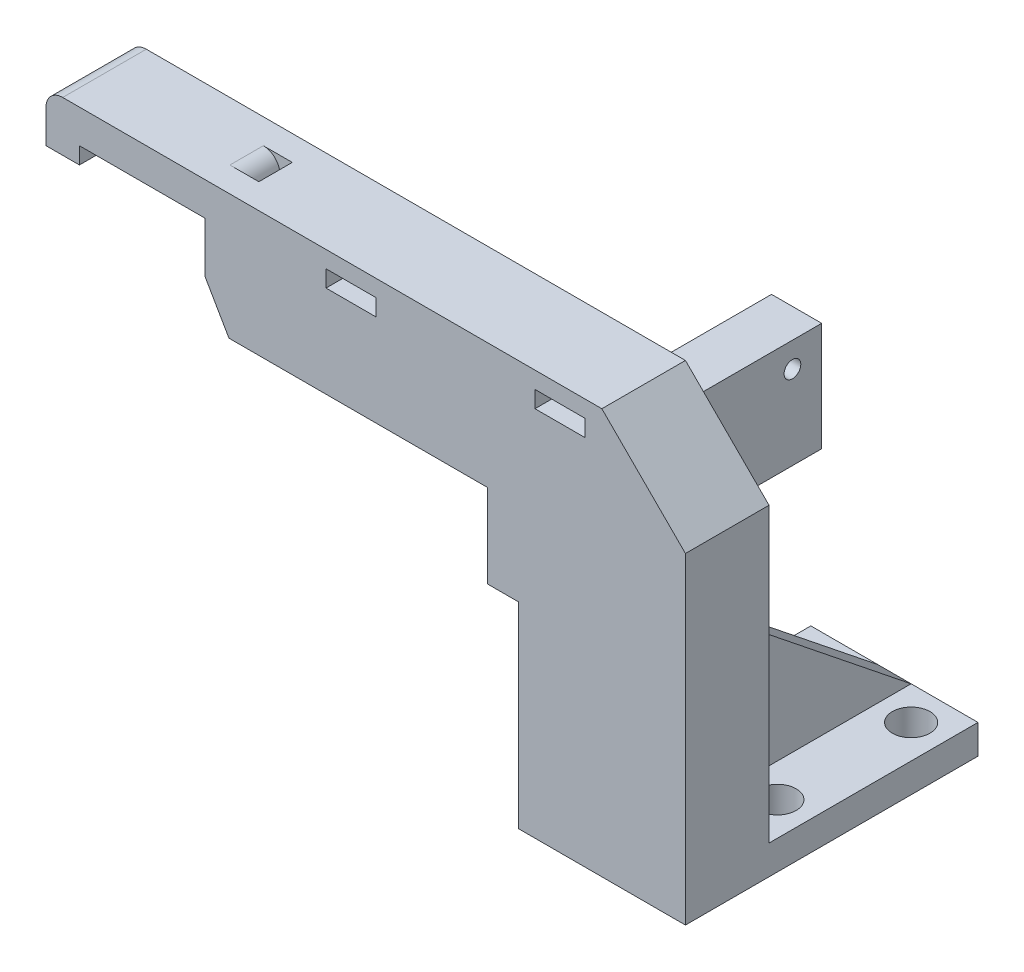
SolidWorks part; units mm, degrees
material "3D printed plastic"
ref_plane "Front Plane" through (0, 0, 0) normal (0, 0, 1) x (1, 0, 0)
ref_plane "Top Plane" through (0, 0, 0) normal (0, 1, 0) x (1, 0, 0)
ref_plane "Right Plane" through (0, 0, 0) normal (1, 0, 0) x (0, 0, -1)
sketch "Sketch1" plane through (0, 0, 0) normal (0, 0, 1) x (1, 0, 0)
  line L0 (-13.7, 36.5) -> (-13.7, 23.5)
  line L1 (-13.7, 23.5) -> (-10, 23.5)
  line L2 (-10, 23.5) -> (-10, 0)
  line L3 (-10, 0) -> (10, 0)
  line L4 (10, 0) -> (10, 36.5)
  line L5 (10, 36.5) -> (-13.7, 36.5)
  line L6 (-13.7, 30) -> (10, 30) construction
  dimension "D1" = 20
  dimension "D2" = 13
  dimension "D3" = 13.7
  dimension "D4" = 30
extrude "Boss-Extrude1" add sketch "Sketch1" along normal blind 10
sketch "Sketch6" plane through (0, 0, 0) normal (0, -1, 0) x (1, 0, 0)
  line L0 (10, 10) -> (10, 0) construction
  line L1 (-10, -25) -> (10, -25)
  line L2 (-10, -25) -> (-10, 0)
  line L3 (-10, 0) -> (10, 0)
  line L4 (10, -25) -> (10, 0)
  dimension "D1" = 25
extrude "Boss-Extrude3" add sketch "Sketch6" against normal blind 3.5
sketch "Sketch8" plane through (0, 0, 0) normal (0, -1, 0) x (1, 0, 0)
  line L0 (-6, -21) -> (-6, -5) construction
  line L1 (-6, -5) -> (6, -5) construction
  line L2 (6, -5) -> (6, -21) construction
  line L3 (6, -21) -> (-6, -21) construction
  line L4 (-6, -5) -> (0, -13) construction
  line L5 (0, -13) -> (6, -21) construction
  line L6 (0, -13) -> (0, 0) construction
  circle A0 centre (-6, -5) radius 2.25
  circle A1 centre (6, -5) radius 2.25
  circle A2 centre (6, -21) radius 2.25
  circle A3 centre (-6, -21) radius 2.25
  dimension "D3" = 4.5
  dimension "D1" = 12
  dimension "D2" = 16
  dimension "D4" = 13
extrude "Cut-Extrude2" cut sketch "Sketch8" against normal through all
sketch "Sketch9" plane through (-13.7, 0, 0) normal (-1, 0, 0) x (0, 0, 1)
  line L0 (10, 23.5) -> (0, 23.5) construction
  line L1 (0, 36.5) -> (-24, 36.5)
  line L2 (0, 36.5) -> (0, 23.5)
  line L3 (0, 23.5) -> (-24, 23.5)
  line L4 (-24, 36.5) -> (-24, 23.5)
  line L5 (0, 36.5) -> (0, 23.5) construction
  dimension "D1" = 24
extrude "Boss-Extrude4" add sketch "Sketch9" against normal blind 6
sketch "Sketch10" plane through (-13.7, 0, 0) normal (-1, 0, 0) x (0, 0, 1)
  line L0 (-13, 27.8) -> (-13, 34.2) construction
  line L1 (10, 0) -> (-25, 0) construction
  circle A0 centre (-13, 34.2) radius 1.1
  circle A1 centre (-13, 27.8) radius 1.1
  dimension "D1" = 2.2
  dimension "D4" = 27.8
  dimension "D2" = 6.4
  dimension "D3" = 13
extrude "Cut-Extrude3" cut sketch "Sketch10" against normal blind 2
sketch "Sketch11" plane through (-13.7, 0, 0) normal (-1, 0, 0) x (0, 0, 1)
  line L0 (-20.5, 33.5) -> (-5.5, 33.5) construction
  line L1 (-13, 27.8) -> (-13, 33.5) construction
  circle A0 centre (-20.5, 33.5) radius 1
  circle A1 centre (-5.5, 33.5) radius 1
  dimension "D1" = 2
  dimension "D2" = 15
  dimension "D3" = 5.7
extrude "Cut-Extrude4" cut sketch "Sketch11" against normal through all
sketch "Sketch12" plane through (0, 0, 10) normal (0, 0, 1) x (1, 0, 0)
  line L0 (-10, 0) -> (10, 0) construction
  line L1 (10, 36.5) -> (-13.7, 36.5)
  line L2 (10, 36.5) -> (10, 48.5)
  line L3 (10, 48.5) -> (-66.5, 48.5)
  line L4 (-66.5, 42.5) -> (-66.5, 48.5)
  line L5 (-62.5, 44.5) -> (-62.5, 42.5)
  line L6 (-66.5, 42.5) -> (-62.5, 42.5)
  line L7 (-62.5, 44.5) -> (-47.5, 44.5)
  line L8 (-47.5, 38.5) -> (-47.5, 44.5)
  line L9 (-55, 44.5) -> (-55, 29.6848) construction
  line L10 (-30, 46.5) -> (-30, 48.5) construction
  line L11 (-33, 46.5) -> (-27, 46.5)
  line L12 (-33, 46.5) -> (-33, 44.5)
  line L13 (-33, 44.5) -> (-27, 44.5)
  line L14 (-27, 46.5) -> (-27, 44.5)
  line L15 (-8, 46.5) -> (-2, 46.5)
  line L16 (-8, 46.5) -> (-8, 44.5)
  line L17 (-8, 44.5) -> (-2, 44.5)
  line L18 (-2, 46.5) -> (-2, 44.5)
  line L19 (-5, 46.5) -> (-5, 48.5) construction
  line L20 (-13.7, 36.5) -> (-13.7, 33.5)
  line L21 (-13.7, 36.5) -> (-13.7, 23.5) construction
  line L22 (-13.7, 33.5) -> (-44.6132, 33.5)
  line L23 (-47.5, 38.5) -> (-44.6132, 33.5)
  dimension "D1" = 12
  dimension "D2" = 66.5
  dimension "D3" = 44.5
  dimension "D4" = 15
  dimension "D5" = 55
  dimension "D6" = 2
  dimension "D7" = 2
  dimension "D8" = 6
  dimension "D9" = 2
  dimension "D10" = 25
  dimension "D11" = 25
  dimension "D12" = 3
  dimension "D13" = 30
  dimension "D14" = 6
extrude "Boss-Extrude5" add sketch "Sketch12" against normal up to surface (10 mm away) up to face at (-0.9, 20.0833, 0)
ref_plane "Plane1" through (0, 0, 5) normal (0, 0, 1) x (1, 0, 0)
sketch "Sketch14" plane through (0, 0, 5) normal (0, 0, 1) x (1, 0, 0)
  line L0 (10, 48.5) -> (-66.5, 48.5) construction
  line L1 (-62.5, 44.5) -> (-66.5, 44.5)
  line L2 (-62.5, 44.5) -> (-62.5, 42.5)
  line L3 (-62.5, 42.5) -> (-66.5, 42.5)
  line L4 (-66.5, 44.5) -> (-66.5, 42.5)
  line L5 (-47.5, 44.5) -> (-47.5, 38.5) construction
  line L6 (-47.5, 44.5) -> (-47.5, 42.5)
  line L7 (-44.0359, 48.5) -> (-47.5, 48.5)
  arc A0 (-47.5, 44.5) -> (-47.5, 48.5) centre (-47.5, 46.5) ccw
  arc A1 (-47.5, 42.5) -> (-44.0359, 48.5) centre (-47.5, 46.5) ccw
  dimension "D1" = 2
extrude "Cut-Extrude5" cut sketch "Sketch14" against normal mid plane 4
ref_plane "Plane2" through (0, 0, 0) normal (1, 0, 0) x (0, 0, -1)
sketch "Sketch15" plane through (0, 0, 0) normal (1, 0, 0) x (0, 0, -1)
  line L0 (0, 3.5) -> (25, 3.5)
  line L1 (0, 3.5) -> (0, 23.5)
  line L2 (0, 3.5) -> (0, 48.5) construction
  line L3 (0, 23.5) -> (25, 3.5)
  dimension "D1" = 20
extrude "Boss-Extrude6" add sketch "Sketch15" along normal mid plane 4
fillet "Fillet1" radius 2 2 edges at (-66.5, 48.5, 5) (-66.5, 44.5, 5)
chamfer "Chamfer1" distance 2 angle 45 1 edges at (-64.5, 42.5, 3)
chamfer "Chamfer2" distance 10 angle 45 1 edges at (10, 48.5, 5)
